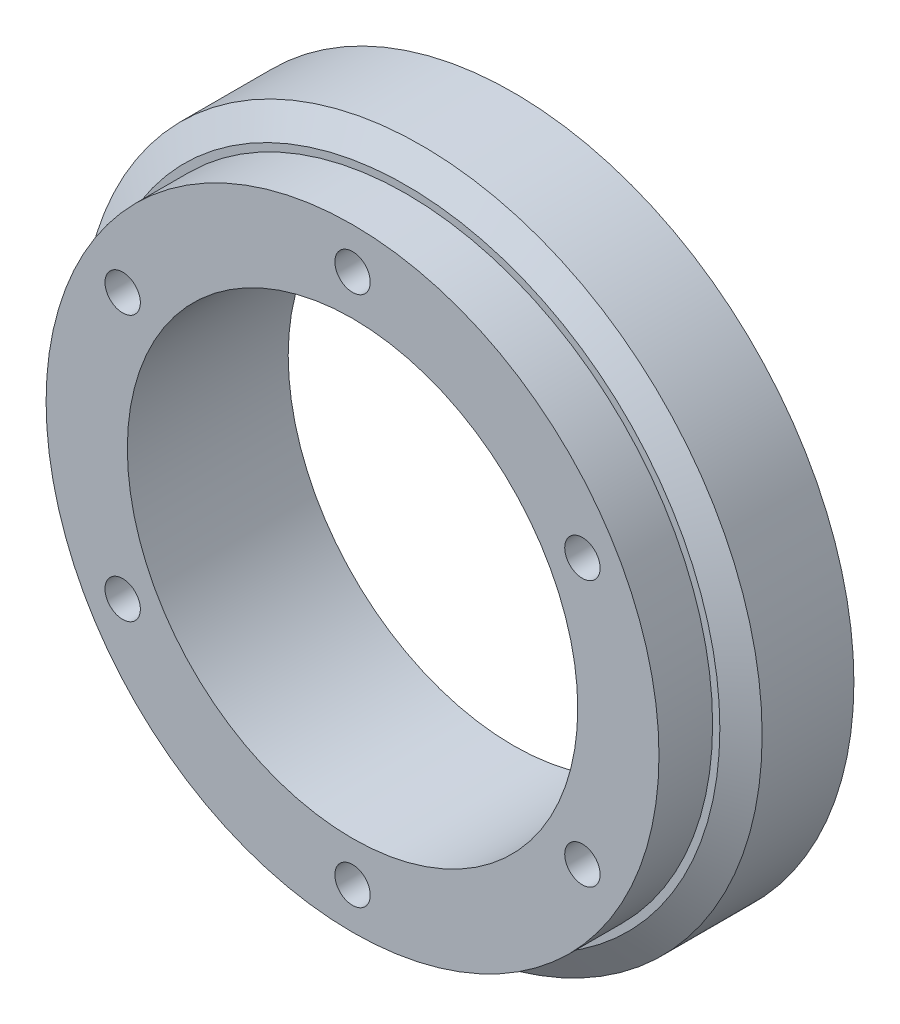
SolidWorks part; units mm, degrees
ref_plane "Front Plane" through (0, 0, 0) normal (0, 0, 1) x (1, 0, 0)
ref_plane "Top Plane" through (0, 0, 0) normal (0, 1, 0) x (1, 0, 0)
ref_plane "Right Plane" through (0, 0, 0) normal (1, 0, 0) x (0, 0, -1)
sketch "Sketch1" plane through (0, 0, 0) normal (1, 0, 0) x (0, 0, -1)
  line L0 (0, 31.75) -> (-8.5566, 31.75)
  line L1 (-8.5566, 31.75) -> (-10, 29.25)
  line L4 (-15, 0) -> (0, 0) construction
  line L9 (-15, 28.575) -> (-15, 21)
  line L10 (-15, 21) -> (0, 21)
  line L11 (0, 21) -> (0, 31.75)
  line L12 (-15, -21) -> (0, -21) construction
  line L13 (-15, -28.575) -> (-15, -21) construction
  line L14 (-10, -29.25) -> (-15, -28.575) construction
  line L15 (-8.5566, -31.75) -> (-10, -29.25) construction
  line L16 (0, -31.75) -> (-8.5566, -31.75) construction
  line L17 (0, -21) -> (0, -31.75) construction
  line L18 (-15, 28.575) -> (-10, 28.575)
  line L19 (-10, 28.575) -> (-10, 29.25)
  dimension "D1" = 63.5
  dimension "D2" = 3.175
  dimension "D3" = 30
  dimension "D4" = 42
  dimension "D5" = 10
  dimension "D6" = 15
  dimension "D7" = 2.5
revolve "Revolve1" add sketch "Sketch1" angle 360 about L4
sketch "Sketch2" plane through (0, 0, 0) normal (0, 0, -1) x (-1, 0, 0)
  circle A0 centre (0, 0) radius 24.75 construction
  point P3 (0, 24.75)
  dimension "D1" = 49.5
hole_wizard "M4x0.7 Tapped Hole1" positions "Sketch2" profile "Sketch3" tap size "M4x0.7" standard "ANSI Metric" end condition through all
sketch "Sketch3" plane through (0, 24.75, 0) normal (1, 0, 0) x (0, 1, 0)
  line L0 (0, 0) -> (0, 15)
  line L1 (0, 15) -> (1.65, 15)
  line L2 (1.65, 15) -> (1.65, 0)
  line L5 (1.65, 0) -> (0, 0)
  line L11 (0, -6.35) -> (0, 107.95) construction
  dimension "Thru Tap Drill Dia." = 3.3
  dimension "Thru Tap Drill Depth" = 15
cosmetic thread "Hole Thread1" parameters "D2"=4
pattern_circular "CirPattern1" count 6 over 360 about axis through (0, 0, 15) along (0, 0, 1) of "M4x0.7 Tapped Hole1"
cosmetic thread "Hole Thread2" parameters "D2"=4
cosmetic thread "Hole Thread3" parameters "D2"=4
cosmetic thread "Hole Thread4" parameters "D2"=4
cosmetic thread "Hole Thread5" parameters "D2"=4
cosmetic thread "Hole Thread6" parameters "D2"=4
